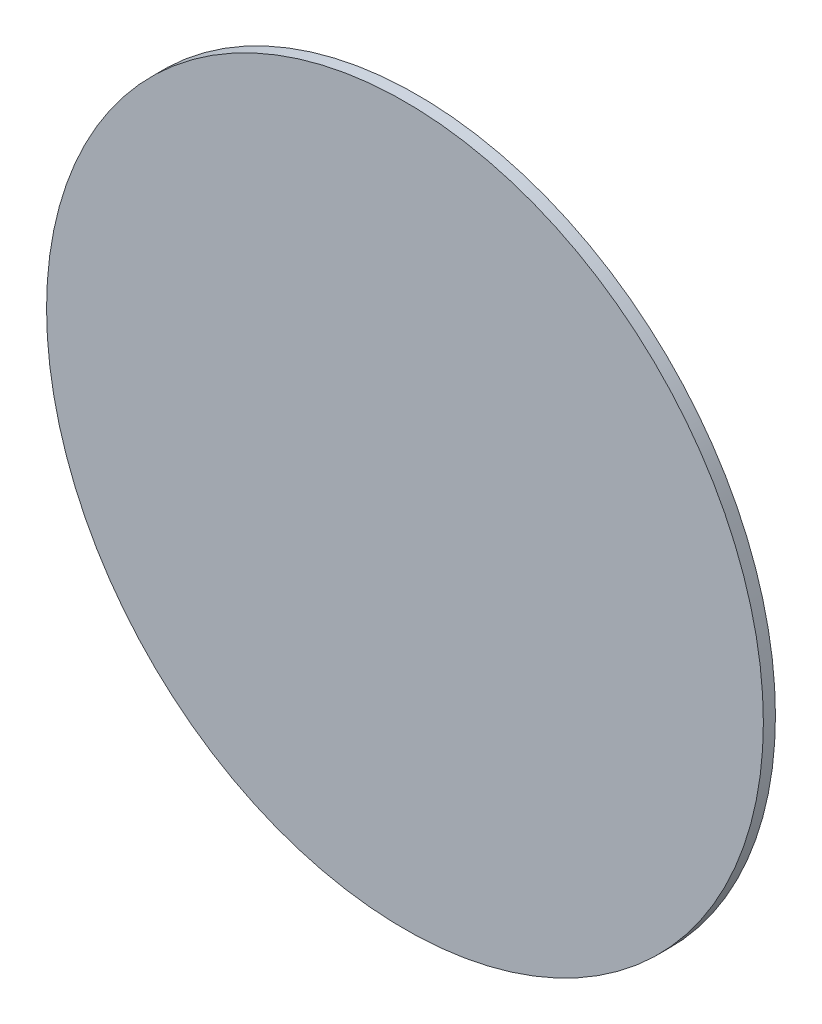
SolidWorks part; units mm, degrees
ref_plane "Plan de face" through (0, 0, 0) normal (0, 0, 1) x (1, 0, 0)
ref_plane "Plan de dessus" through (0, 0, 0) normal (0, 1, 0) x (1, 0, 0)
ref_plane "Plan de droite" through (0, 0, 0) normal (1, 0, 0) x (0, 0, -1)
sketch "Esquisse1" plane through (0, 0, 0) normal (0, 0, 1) x (1, 0, 0)
  circle A0 centre (0, 0) radius 47.5
  dimension "D1" = 95
extrude "Boss.-Extru.1" add sketch "Esquisse1" along normal blind 1.6
